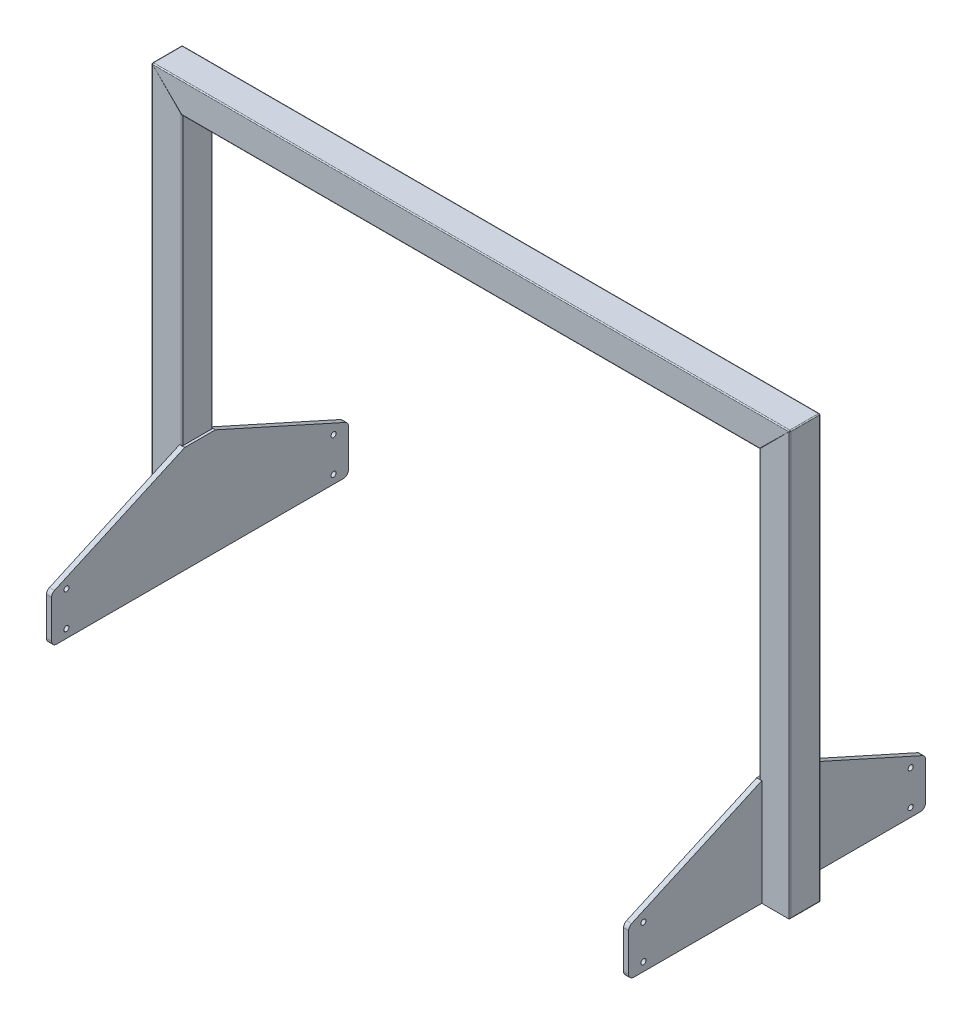
SolidWorks part; units mm, degrees
ref_plane "Front Plane" through (0, 0, 0) normal (0, 0, 1) x (1, 0, 0)
ref_plane "Top Plane" through (0, 0, 0) normal (0, 1, 0) x (1, 0, 0)
ref_plane "Right Plane" through (0, 0, 0) normal (1, 0, 0) x (0, 0, -1)
sketch "Sketch1" plane through (0, 0, 0) normal (0, 0, 1) x (1, 0, 0)
  line L0 (-298.1152, -200) -> (-298.1152, 200) construction
  line L1 (-298.1152, 200) -> (298.12, 200) construction
  line L2 (298.12, 200) -> (298.12, -200) construction
  line L3 (-283.1152, -200) -> (-283.1152, 184.8228)
  line L4 (-282.7239, 185) -> (282.7287, 185)
  line L5 (283.12, 184.8228) -> (283.12, -200)
  line L6 (-313.1152, -200) -> (-313.1152, 215)
  line L7 (-313.1152, 215) -> (313.12, 215)
  line L8 (313.12, 215) -> (313.12, -200)
  line L9 (-313.1152, -200) -> (-283.1152, -200)
  line L10 (283.12, -200) -> (313.12, -200)
  line L11 (283.12, 184.8228) -> (312.7767, 214.5732)
  line L12 (312.7767, 214.5732) -> (282.7287, 185)
  line L13 (283.12, 185) -> (283.12, -200) construction
  line L14 (-283.1152, 185) -> (283.12, 185) construction
  line L15 (0.0024, 215) -> (0.0024, 578.8739) construction
  line L16 (-312.7719, 214.5732) -> (-282.7239, 185)
  line L17 (-283.1152, 184.8228) -> (-312.7719, 214.5732)
  line L18 (-283.1152, -200) -> (-283.1152, 185) construction
  dimension "D1" = 596.2352
  dimension "D2" = 400
  dimension "D3" = 298.12
  dimension "D4" = 200
  dimension "D5" = 15
  dimension "D6" = 15
extrude "Boss-Extrude1" add sketch "Sketch1" along normal mid plane 30
sketch "Sketch2" plane through (283.12, 0, 0) normal (-1, 0, 0) x (0, 0, 1)
  line L0 (-15, -95.7312) -> (-142.7252, -153.2971)
  line L1 (-15, 215) -> (-15, -200) construction
  line L2 (-145.6707, -157.8555) -> (-145.6707, -195)
  line L3 (-140.6707, -200) -> (140.6707, -200)
  line L5 (-15, -95.7312) -> (15, -95.7312)
  line L6 (0, 0) -> (0, -251.7251) construction
  line L7 (145.6707, -157.8555) -> (145.6707, -195)
  line L8 (15, -95.7312) -> (142.7252, -153.2971)
  arc A0 (-145.6707, -195) -> (-140.6707, -200) centre (-140.6707, -195) ccw
  arc A1 (-142.7252, -153.2971) -> (-145.6707, -157.8555) centre (-140.6707, -157.8555) ccw
  circle A2 centre (-131.0963, -157.8555) radius 2.5
  circle A3 centre (-131.0963, -191.5578) radius 2.5
  circle A4 centre (131.0963, -191.5578) radius 2.5
  circle A5 centre (131.0963, -157.8555) radius 2.5
  arc A6 (142.7252, -153.2971) -> (145.6707, -157.8555) centre (140.6707, -157.8555) cw
  arc A7 (145.6707, -195) -> (140.6707, -200) centre (140.6707, -195) cw
  point P8 (0, -200)
  point P29 (0, -95.7312)
  dimension "D1" = 5
  dimension "D2" = 5
extrude "Boss-Extrude2" add sketch "Sketch2" along normal mid plane 5
mirror "Mirror2" about plane through (0, 0, 0) normal (1, 0, 0) of "Boss-Extrude2"
fillet "Fillet1" radius 1 18 edges at (-282.7239, 185, 0) (0.0024, 185, 15) (282.7287, 185, 0) (0.0024, 185, -15) (-313.1152, 7.5, 15) (-313.1152, -200, 0) (-313.1152, 7.5, -15) (313.12, -200, 0) (313.12, 7.5, 15) (313.12, 7.5, -15) (313.12, 215, 0) (0.0024, 215, 15) (-313.1152, 215, 0) (0.0024, 215, -15) (283.12, 44.5458, 15) (283.12, 44.5458, -15) (-283.1152, 44.5458, -15) (-283.1152, 44.5458, 15)
